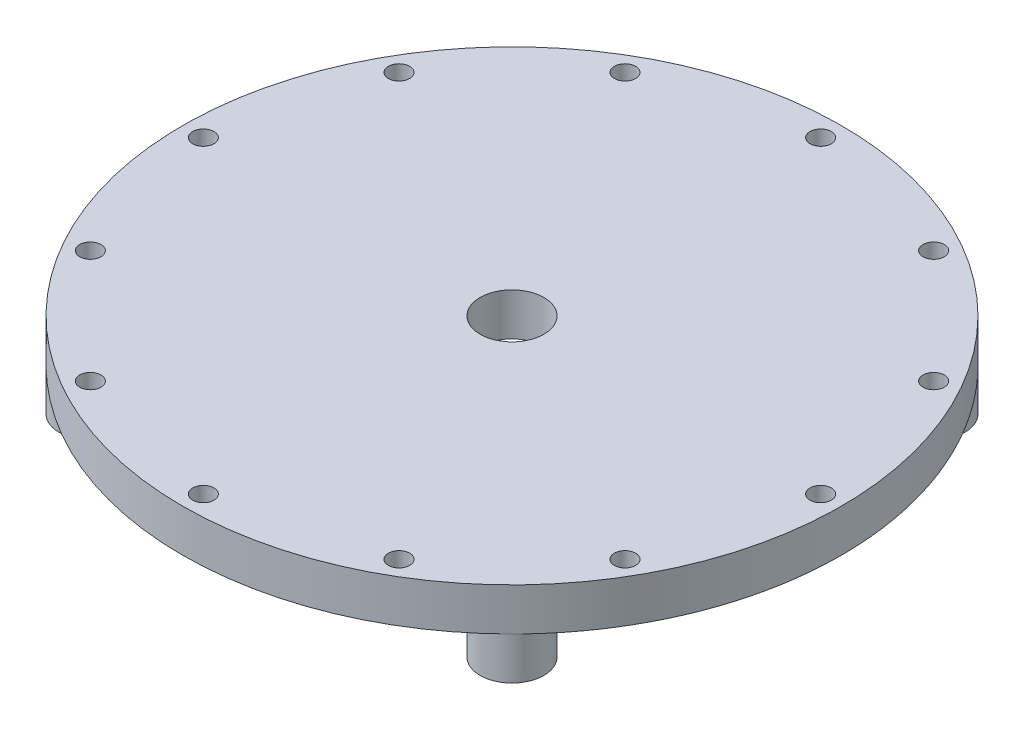
SolidWorks part; units mm, degrees
ref_plane "Front Plane" through (0, 0, 0) normal (0, 0, 1) x (1, 0, 0)
ref_plane "Top Plane" through (0, 0, 0) normal (0, 1, 0) x (1, 0, 0)
ref_plane "Right Plane" through (0, 0, 0) normal (1, 0, 0) x (0, 0, -1)
sketch "Sketch2" plane through (0, 0, 0) normal (0, 1, 0) x (1, 0, 0)
  circle A0 centre (0, 0) radius 98.425
  dimension "D1" = 196.85
extrude "Boss-Extrude1" add sketch "Sketch2" along normal blind 12.7
sketch "Sketch3" plane through (0, 0, 0) normal (0, 1, 0) x (1, 0, 0)
  circle A0 centre (0, 0) radius 9.525
  dimension "D1" = 19.05
extrude "Cut-Extrude4" cut sketch "Sketch3" against normal blind 12.7 and the other way blind 12.7
sketch "Sketch5" plane through (0, 0, 0) normal (0, 1, 0) x (1, 0, 0)
  line L0 (0, -98.425) -> (56.9174, -98.425) construction
  line L1 (0, -95.377) -> (-5.5754, -95.377) construction
  circle A0 centre (0, -92.202) radius 3.175
  circle A1 centre (0, 0) radius 98.425 construction
  point P9 (20.7275, -89.842)
  dimension "D1" = 6.35
  dimension "D2" = 92.202
extrude "Cut-Extrude9" cut sketch "Sketch5" against normal blind 2.54 and the other way up to next
pattern_circular "CirPattern1" count 12 over 360 about axis through (0, 12.7, 0) along (0, -1, 0) of "Cut-Extrude9"
sketch "Sketch6" plane through (0, 0, 0) normal (0, 1, 0) x (-1, 0, 0)
  line L0 (62.8618, 62.8618) -> (0, 0) construction
  line L1 (0, 0) -> (116.3449, 0) construction
  line L2 (6.985, 0) -> (-6.985, 0) construction
  circle A0 centre (0, 0) radius 88.9 construction
  circle A1 centre (62.8618, 62.8618) radius 9.525
  dimension "D1" = 177.8
  dimension "D2" = 19.05
  dimension "D3" = 45
extrude "Boss-Extrude2" add sketch "Sketch6" against normal blind 12.7
sketch "Sketch8" plane through (0, 0, 0) normal (0, 1, 0) x (1, 0, 0)
  circle A0 centre (-62.8618, -62.8618) radius 3.175
  dimension "D1" = 6.35
extrude "Cut-Extrude10" cut sketch "Sketch8" along normal blind 15.24 from surface starting at face at (-62.8618, -12.7, 72.3868)
pattern_circular "CirPattern2" count 4 over 360 about axis through (0, 12.7, 0) along (0, -1, 0) of "Boss-Extrude2", "Cut-Extrude10" reverse direction yes
